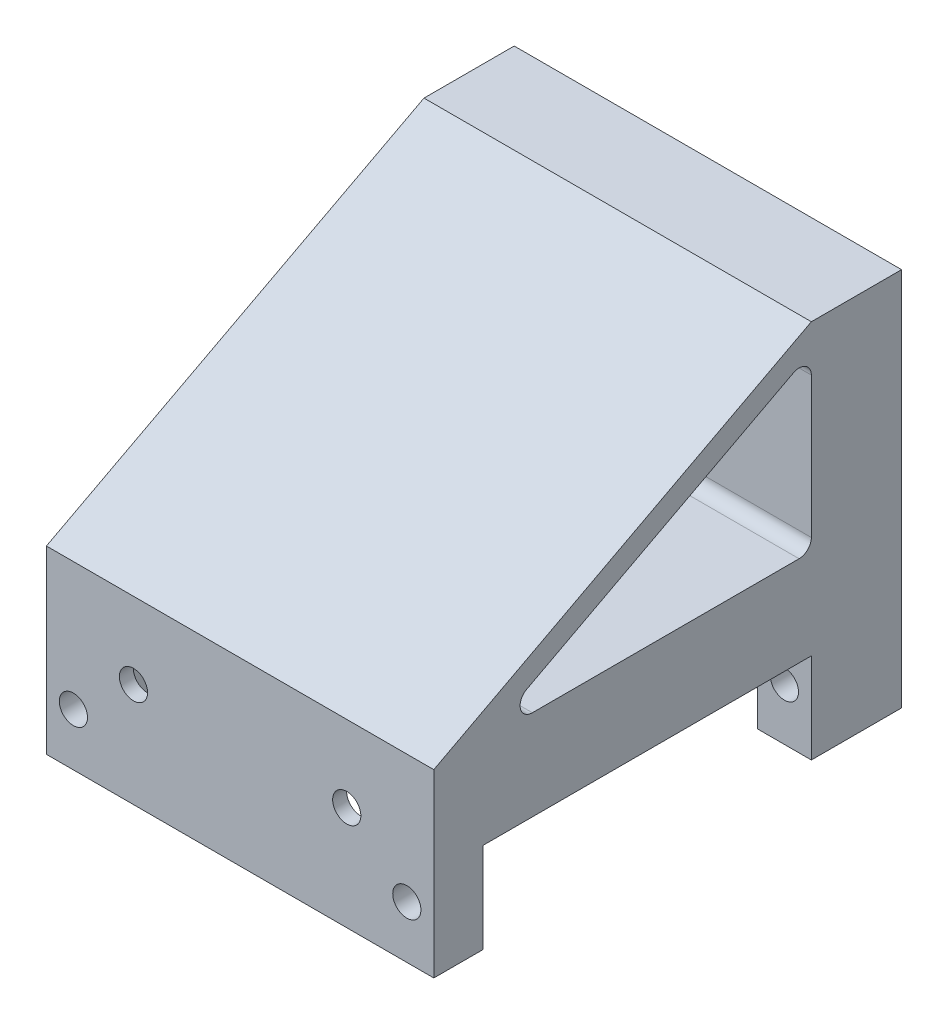
SolidWorks part; units mm, degrees
ref_plane "Front Plane" through (0, 0, 0) normal (0, 0, 1) x (1, 0, 0)
ref_plane "Top Plane" through (0, 0, 0) normal (0, 1, 0) x (1, 0, 0)
ref_plane "Right Plane" through (0, 0, 0) normal (1, 0, 0) x (0, 0, -1)
sketch "Sketch1" plane through (0, 0, 0) normal (1, 0, 0) x (0, 0, -1)
  line L0 (0, -3.0523) -> (0, 36.2705)
  line L1 (-9.3472, 36.2705) -> (-48.4632, 15.6421)
  line L2 (-48.4632, 15.6421) -> (-48.4632, -3.0523)
  line L3 (-48.4632, -3.0523) -> (-43.3832, -3.0523)
  line L4 (-43.3832, -3.0523) -> (-43.3832, 6.2949)
  line L5 (-43.3832, 6.2949) -> (-9.3472, 6.2949)
  line L6 (-9.3472, 6.2949) -> (-9.3472, -3.0523)
  line L7 (-9.3472, -3.0523) -> (0, -3.0523)
  line L8 (-9.3472, 36.2705) -> (0, 36.2705)
  line L9 (-43.3832, 15.6421) -> (-9.3472, 33.5915)
  line L10 (-9.3472, 33.5915) -> (-9.3472, 15.6421)
  line L11 (-9.3472, 15.6421) -> (-43.3832, 15.6421)
  dimension "D1" = 34.036
  dimension "D2" = 5.08
  dimension "D3" = 9.3472
  dimension "D4" = 9.3472
  dimension "D5" = 9.3472
extrude "Boss-Extrude1" add sketch "Sketch1" along normal blind 40.132
fillet "Fillet1" radius 1.27 3 edges at (20.066, 15.6421, 43.3832) (20.066, 33.5915, 9.3472) (20.066, 15.6421, 9.3472)
sketch "Sketch2" plane through (0, 6.2949, 0) normal (0, -1, 0) x (1, 0, 0)
  line L0 (40.132, 43.3832) -> (0, 43.3832) construction
  line L1 (5.9182, 43.3832) -> (34.2138, 43.3832)
  line L2 (5.9182, 43.3832) -> (5.9182, 9.3472)
  line L3 (5.9182, 9.3472) -> (34.2138, 9.3472)
  line L4 (34.2138, 43.3832) -> (34.2138, 9.3472)
  line L5 (40.132, 9.3472) -> (0, 9.3472) construction
  line L6 (0, 43.3832) -> (0, 9.3472) construction
  line L7 (40.132, 43.3832) -> (40.132, 9.3472) construction
  dimension "D1" = 5.9182
  dimension "D2" = 5.9182
extrude "Cut-Extrude1" cut sketch "Sketch2" against normal blind 4.4704
chamfer "Chamfer1" distance 5.08 angle 56 2 edges at (5.9182, 6.2949, 26.3652) (34.2138, 6.2949, 26.3652) first distance on face at (2.9591, 6.2949, 26.3652) first distance on face at (37.1729, 6.2949, 26.3652)
sketch "Sketch3" plane through (0, 0, 0) normal (0, 0, -1) x (-1, 0, 0)
  line L0 (-3.8535, 10.7653) -> (-36.2785, 10.7653) construction
  line L1 (-40.132, -3.0523) -> (-40.132, 36.2705) construction
  line L2 (0, -3.0523) -> (0, 36.2705) construction
  circle A1 centre (-37.338, 2.3833) radius 1.4605
  circle A2 centre (-31.115, 7.7173) radius 1.4605
  circle A3 centre (-9.017, 7.7173) radius 1.4605
  circle A4 centre (-2.794, 2.3833) radius 1.4605
  dimension "D1" = 2.794
  dimension "D2" = 2.921
  dimension "D3" = 2.921
  dimension "D4" = 2.921
  dimension "D5" = 2.921
  dimension "D6" = 2.794
  dimension "D12" = 9.017
  dimension "D8" = 8.382
  dimension "D9" = 8.382
  dimension "D7" = 3.048
  dimension "D10" = 3.048
  dimension "D11" = 22.098
extrude "Cut-Extrude2" cut sketch "Sketch3" against normal through all
sketch "Sketch4" plane through (0, -3.0523, 0) normal (0, -1, 0) x (1, 0, 0)
  line L0 (40.132, 9.3472) -> (0, 9.3472) construction
  line L1 (5.588, 47.0154) -> (34.544, 47.0154)
  line L2 (5.588, 47.0154) -> (5.588, 5.715)
  line L3 (5.588, 5.715) -> (34.544, 5.715)
  line L4 (34.544, 47.0154) -> (34.544, 5.715)
  line L5 (36.2785, 43.3832) -> (3.8535, 43.3832) construction
  line L6 (0, 43.3832) -> (0, 9.3472) construction
  line L8 (40.132, 43.3832) -> (40.132, 9.3472) construction
  dimension "D1" = 3.6322
  dimension "D2" = 3.6322
  dimension "D3" = 5.588
  dimension "D4" = 5.588
extrude "Cut-Extrude4" cut sketch "Sketch4" against normal up to surface (13.8176 mm away) up to face at (20.066, 10.7653, 26.3652)
